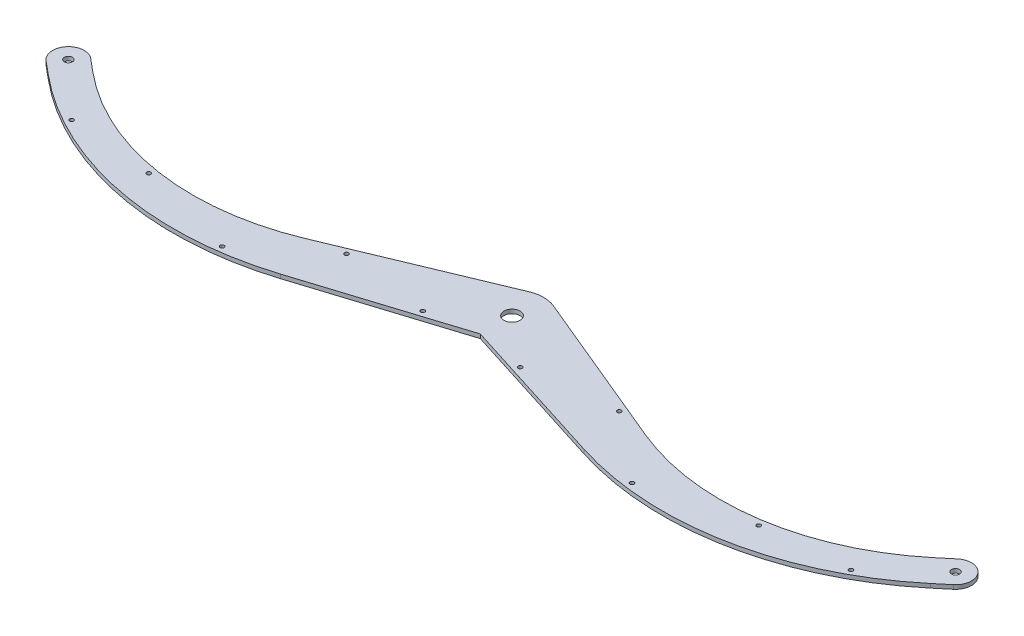
SolidWorks part; units mm, degrees
ref_plane "Front Plane" through (0, 0, 0) normal (0, 0, 1) x (1, 0, 0)
ref_plane "Top Plane" through (0, 0, 0) normal (0, 1, 0) x (1, 0, 0)
ref_plane "Right Plane" through (0, 0, 0) normal (1, 0, 0) x (0, 0, -1)
sketch "Sketch1" plane through (0, 0, 0) normal (0, 1, 0) x (1, 0, 0)
  line L0 (0, 0) -> (-350, 0) construction
  line L1 (-341.9905, 9.5967) -> (-332.022, 1.277)
  line L2 (-134.0614, -28.7384) -> (-9.6095, 23.0794)
  line L3 (-358.0095, -9.5967) -> (-348.0411, -17.9165)
  line L4 (-119.8393, -62.8958) -> (0, -25)
  line L5 (-332.022, 1.277) -> (-348.0411, -17.9165) construction
  line L6 (-134.0614, -28.7384) -> (-119.8393, -62.8958) construction
  line L7 (0, -25) -> (0, 25) construction
  line L8 (119.8393, -62.8958) -> (0, -25)
  line L9 (134.0614, -28.7384) -> (9.6095, 23.0794)
  line L10 (358.0095, -9.5967) -> (348.0411, -17.9165)
  line L11 (341.9905, 9.5967) -> (332.022, 1.277)
  arc A0 (9.6095, 23.0794) -> (-9.6095, 23.0794) centre (0, 0) ccw
  arc A1 (-341.9905, 9.5967) -> (-358.0095, -9.5967) centre (-350, 0) ccw
  arc A2 (-332.022, 1.277) -> (-134.0614, -28.7384) centre (-208.2874, 149.5319) ccw
  arc A3 (-348.0411, -17.9165) -> (-119.8393, -62.8958) centre (-192.8592, 168.0174) ccw
  arc A4 (348.0411, -17.9165) -> (119.8393, -62.8958) centre (192.8592, 168.0174) cw
  arc A5 (332.022, 1.277) -> (134.0614, -28.7384) centre (208.2874, 149.5319) cw
  arc A6 (341.9905, 9.5967) -> (358.0095, -9.5967) centre (350, 0) cw
  dimension "D1" = 25
  dimension "D3" = 25
  dimension "D6" = 242.1835
  dimension "D7" = 193.1056
  dimension "D2" = 350
  dimension "D4" = 25
  dimension "D5" = 37
  dimension "D8" = 50
extrude "Boss-Extrude1" add sketch "Sketch1" along normal blind 3.18
sketch "Sketch3" plane through (0, 3.18, 0) normal (0, 1, 0) x (1, 0, 0)
  line L0 (0, 25) -> (0, -25) construction
  line L1 (-350, 0) -> (0, 0) construction
  circle A0 centre (-350, 0) radius 3.175
  arc A1 (9.6095, 23.0794) -> (-9.6095, 23.0794) centre (0, 0) ccw construction
  circle A6 centre (-307.4085, -40) radius 1.59
  circle A7 centre (-240.6429, -46) radius 1.59
  circle A8 centre (-161.6663, -67) radius 1.59
  circle A9 centre (-107.5686, -23) radius 1.59
  circle A10 centre (38.4187, -32) radius 1.59
  circle A11 centre (107.5686, -23) radius 1.59
  circle A12 centre (-38.4187, -32) radius 1.59
  circle A13 centre (0, 0) radius 6.35
  circle A15 centre (161.6663, -67) radius 1.59
  circle A16 centre (240.6429, -46) radius 1.59
  circle A17 centre (307.4085, -40) radius 1.59
  circle A18 centre (350, 0) radius 3.175
  dimension "D1" = 6.35
  dimension "D2" = 3.18
  dimension "D3" = 12.7
  dimension "D4" = 50
  dimension "D5" = 110
  dimension "D6" = 175
  dimension "D7" = 245
  dimension "D8" = 310
  dimension "D9" = 40
  dimension "D10" = 46
  dimension "D11" = 67
  dimension "D12" = 23
  dimension "D13" = 32
extrude "Cut-Extrude1" cut sketch "Sketch3" against normal through all
